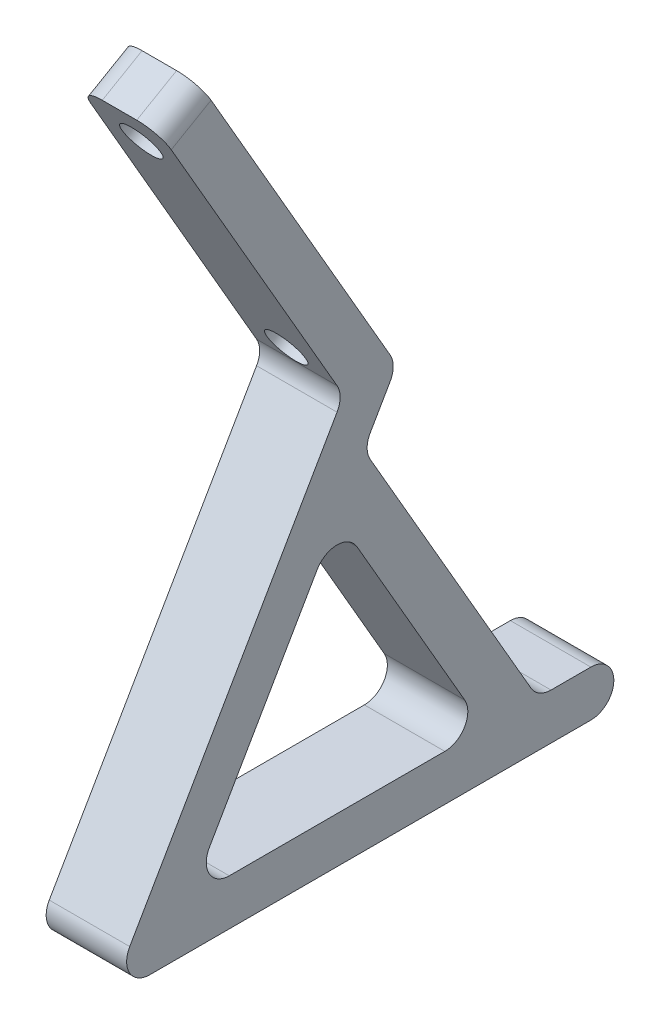
SolidWorks part; units mm, degrees
ref_plane "Plan de face" through (0, 0, 0) normal (0, 0, 1) x (1, 0, 0)
ref_plane "Plan de dessus" through (0, 0, 0) normal (0, 1, 0) x (1, 0, 0)
ref_plane "Plan de droite" through (0, 0, 0) normal (1, 0, 0) x (0, 0, -1)
sketch "Esquisse1" plane through (0, 0, 0) normal (1, 0, 0) x (0, 0, -1)
  line L1 (-37.5, 64.9519) -> (-40.9641, 62.9519)
  line L2 (-40.9641, 62.9519) -> (-24.9641, 35.2391)
  line L3 (-24.9641, 35.2391) -> (-45.3094, 0)
  line L4 (-45.3094, 0) -> (0, 0)
  line L5 (-38.3812, 4) -> (-12.7017, 4)
  line L6 (-12.7017, 4) -> (-25.5415, 26.2391)
  line L7 (-25.5415, 26.2391) -> (-38.3812, 4)
  line L8 (-12.7017, 4) -> (-12.7017, 0) construction
  line L9 (-37.5, 64.9519) -> (-20.3453, 35.2391)
  line L10 (-38.3812, 4) -> (-41.8453, 6) construction
  line L12 (-2.3094, 4) -> (0, 0)
  line L13 (-20.3453, 35.2391) -> (-23.2321, 30.2391)
  line L14 (-23.2321, 30.2391) -> (-8.0829, 4)
  line L15 (-8.0829, 4) -> (-2.3094, 4)
  line L16 (-25.5415, 26.2391) -> (-22.0774, 28.2391) construction
  point P8 (-25.5677, 24.4615)
  point P17 (-12.7397, 11.2548)
  point P18 (-6.5033, 11.2548)
  point P19 (0, 0)
  point P20 (-2.5688, 4.4492)
  dimension "D1" = 120
  dimension "D2" = 4
  dimension "D3" = 32
  dimension "D4" = 75
  dimension "D5" = 5
extrude "Boss.-Extru.1" add sketch "Esquisse1" along normal blind 7
hole_wizard "Dégagement M31" positions "Esquisse2" profile "Esquisse3" hole size "M3" standard "ISO" end condition through all
sketch "Esquisse2" plane through (0, 0, 0) normal (0, 0.5, -0.866) x (-1, 0, 0)
  line L0 (-7, 75) -> (-3.5, 71.2) construction
  line L1 (-3.5, 71.2) -> (0, 75) construction
  line L3 (-3.5, 46) -> (-3.5, 71.2) construction
  line L6 (0, 40.6906) -> (0, 75) construction
  line L7 (-7, 75) -> (0, 75) construction
  point P0 (-3.5, 71.2)
  point P2 (-3.5, 46)
  point P19 (-7, 75)
  point P20 (-7, 75)
  point P22 (0, 0)
  point P23 (0, 75)
  point P28 (-0.7697, 75)
  dimension "D1" = 25.2
  dimension "D2" = 3.8
sketch "Esquisse3" plane through (3.5, 61.661, 35.6) normal (1, 0, 0) x (0, 0.866, 0.5)
  line L0 (0, 0) -> (0, 39.2391)
  line L1 (0, 39.2391) -> (1.7, 39.2391)
  line L2 (1.7, 39.2391) -> (1.7, 0)
  line L5 (1.7, 0) -> (0, 0)
  line L11 (0, -6.35) -> (0, 107.95) construction
  dimension "Diamètre du perçage jusqu'au prochain" = 3.4
  dimension "Profondeur du perçage jusqu'au prochain" = 39.2391
fillet "Congé1" radius 2 12 edges at (3.5, 4, 38.3812) (3.5, 4, 12.7017) (3.5, 26.2391, 25.5415) (3.5, 35.2391, 24.9641) (3.5, 0, 45.3094) (7, 63.9519, 39.2321) (0, 63.9519, 39.2321) (3.5, 35.2391, 20.3453) (3.5, 30.2391, 23.2321) (3.5, 4, 8.0829) (3.5, 4, 2.3094) (3.5, 0, 0)
